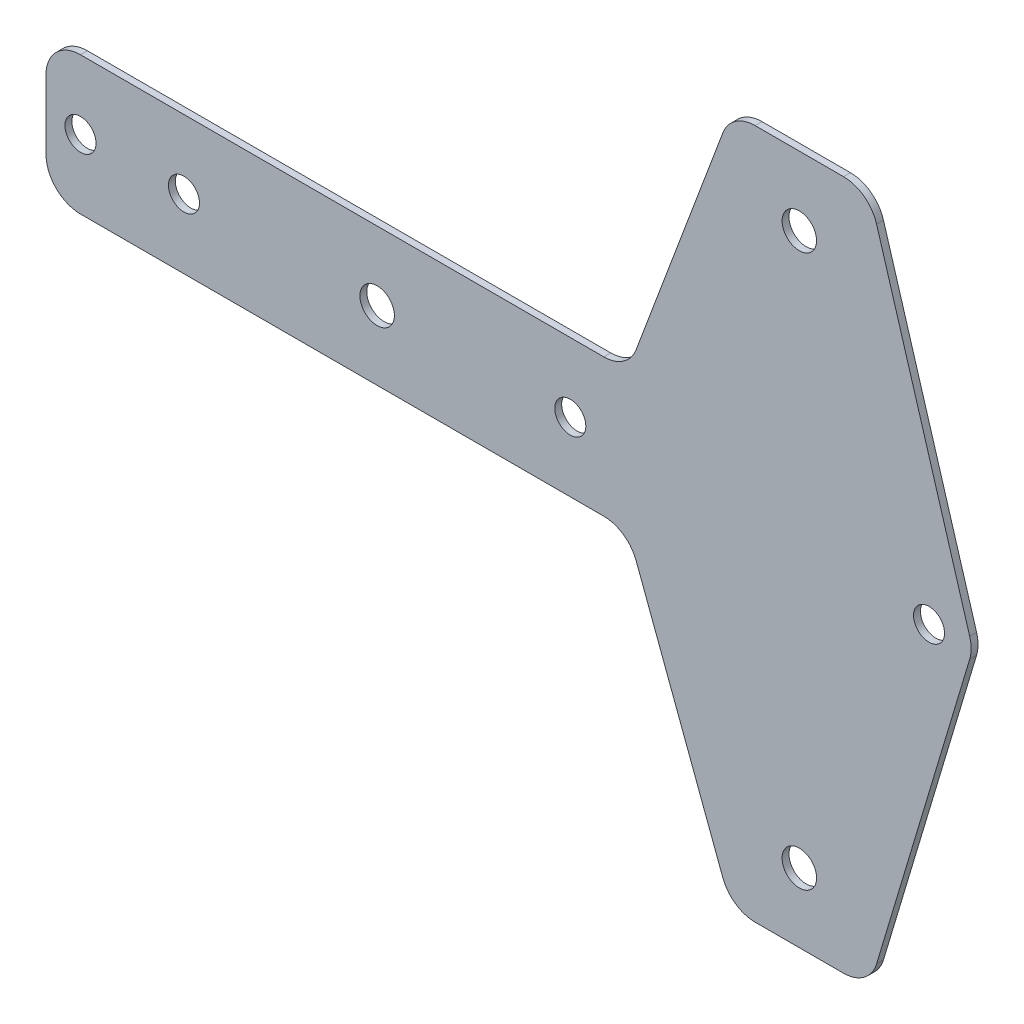
SolidWorks part; units mm, degrees
ref_plane "Front Plane" through (0, 0, 0) normal (0, 0, 1) x (1, 0, 0)
ref_plane "Top Plane" through (0, 0, 0) normal (0, 1, 0) x (1, 0, 0)
ref_plane "Right Plane" through (0, 0, 0) normal (1, 0, 0) x (0, 0, -1)
sketch "Sketch2" plane through (0, 0, 0) normal (0, 0, 1) x (1, 0, 0)
  line L9 (-62.1638, 10) -> (13.6988, 10)
  line L10 (18.3804, 13.2444) -> (30.9471, 46.7556)
  line L11 (35.6288, 50) -> (48.4436, 50)
  line L12 (53.2328, 46.4367) -> (66.7328, 1.4367)
  line L13 (66.7328, -1.4367) -> (53.2328, -46.4367)
  line L14 (48.4436, -50) -> (35.6288, -50)
  line L15 (30.9471, -46.7556) -> (18.3804, -13.2444)
  line L16 (13.6988, -10) -> (-62.1638, -10)
  line L17 (-67.1638, -5) -> (-67.1638, 5)
  line L18 (-67.1638, 0) -> (67.1638, 0) construction
  line L19 (17.1638, -10) -> (17.1638, 10) construction
  line L20 (32.1638, 50) -> (32.1638, -50) construction
  line L21 (52.1638, -50) -> (52.1638, 50) construction
  line L22 (-19.1638, 0) -> (0, 0) construction
  line L23 (0, 0) -> (42.0362, 0) construction
  line L24 (42.0362, 40) -> (42.0362, -40) construction
  arc A9 (13.6988, 10) -> (18.3804, 13.2444) centre (13.6988, 15) ccw
  arc A10 (30.9471, 46.7556) -> (35.6288, 50) centre (35.6288, 45) cw
  arc A11 (48.4436, 50) -> (53.2328, 46.4367) centre (48.4436, 45) cw
  arc A12 (66.7328, 1.4367) -> (66.7328, -1.4367) centre (61.9436, 0) cw
  arc A13 (53.2328, -46.4367) -> (48.4436, -50) centre (48.4436, -45) cw
  arc A14 (35.6288, -50) -> (30.9471, -46.7556) centre (35.6288, -45) cw
  arc A15 (18.3804, -13.2444) -> (13.6988, -10) centre (13.6988, -15) ccw
  arc A16 (-62.1638, -10) -> (-67.1638, -5) centre (-62.1638, -5) cw
  arc A17 (-62.1638, 10) -> (-67.1638, 5) centre (-62.1638, 5) ccw
  circle A18 centre (-19.1638, 0) radius 2.5
  circle A19 centre (42.0362, 40) radius 2.5
  circle A20 centre (42.0362, -40) radius 2.5
  circle A21 centre (-62.1638, 0) radius 2.25
  circle A22 centre (-47.1638, 0) radius 2.25
  circle A23 centre (8.8362, 0) radius 2.25
  circle A24 centre (60.8362, 0) radius 2.25
  point P10 (32.1638, 0)
  point P49 (42.0362, -50)
  dimension "D7" = 20
  dimension "D5" = 5
  dimension "D9" = 5
  dimension "D11" = 4.5
  dimension "D12" = 5
  dimension "D13" = 52
  dimension "D14" = 15
  dimension "D15" = 28
  dimension "D10" = 28
  dimension "D16" = 61.2
  dimension "D1" = 15
  dimension "D2" = 20
  dimension "D3" = 15
  dimension "D4" = 100
  dimension "D8" = 80
base flange "Base-Flange1" sketch "Sketch2" thickness 1 reverse thickness direction no parameters "D1"=0.7366
sketch "Bend-Lines1" [suppressed] plane through (0, 0, 0) normal (0, 1, 0) x (1, 0, 0)
sketch "Bounding-Box1" [suppressed] plane through (0, 0, 0) normal (0, 1, 0) x (1, 0, 0)
sheet metal parameters "Sheet-Metal1" thickness 1 parameters "D1"=0.7366
flat pattern "Flat-Pattern1" [suppressed]
sketch "Bend-Lines2" plane through (0, 0, 0) normal (0, 1, 0) x (1, 0, 0)
sketch3d "Bounding-Box2" [suppressed]
  line L0 (-48.7283, -99.5449, 0) -> (72.8019, -49.8355, 0) construction
  line L1 (-85.8872, -8.6984, 0) -> (35.6431, 41.011, 0) construction
  line L2 (-48.7283, -99.5449, 0) -> (-85.8872, -8.6984, 0) construction
  line L3 (72.8019, -49.8355, 0) -> (35.6431, 41.011, 0) construction
